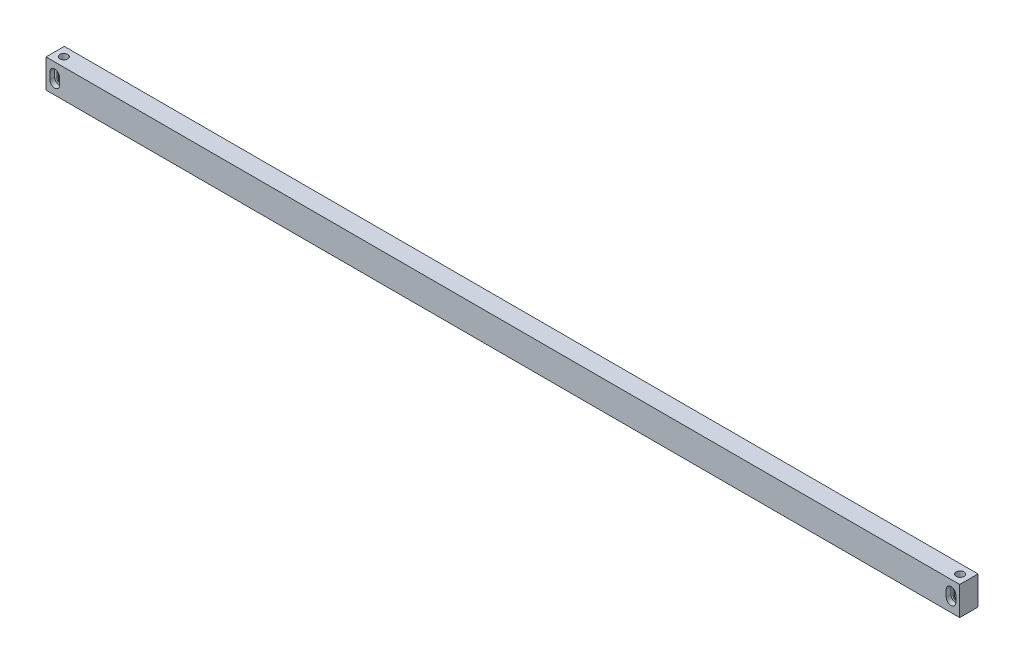
SolidWorks part; units mm, degrees
ref_plane "Front Plane" through (0, 0, 0) normal (0, 0, 1) x (1, 0, 0)
ref_plane "Top Plane" through (0, 0, 0) normal (0, 1, 0) x (1, 0, 0)
ref_plane "Right Plane" through (0, 0, 0) normal (1, 0, 0) x (0, 0, -1)
sketch "Sketch1" plane through (0, 0, 0) normal (0, 0, 1) x (1, 0, 0)
  line L0 (505, 33) -> (505, 0) construction
  line L1 (0, 0) -> (1010, 0)
  line L2 (0, 0) -> (0, 33)
  line L3 (0, 33) -> (1010, 33)
  line L4 (1010, 0) -> (1010, 33)
  line L5 (0, 0) -> (-20, 0)
  line L6 (0, 0) -> (0, 33)
  line L7 (0, 33) -> (-20, 33)
  line L8 (-20, 0) -> (-20, 33)
  line L9 (1010, 33) -> (1030, 33)
  line L10 (1010, 33) -> (1010, 0)
  line L11 (1010, 0) -> (1030, 0)
  line L12 (1030, 33) -> (1030, 0)
  line L13 (-10, 20.5) -> (-10, 12.5) construction
  line L14 (-7, 20.5) -> (-7, 12.5)
  line L15 (-13, 20.5) -> (-13, 12.5)
  line L16 (-4.5, 20.5) -> (-4.5, 12.5)
  line L17 (-15.5, 20.5) -> (-15.5, 12.5)
  line L18 (1020, 20.5) -> (1020, 12.5) construction
  line L19 (1017, 20.5) -> (1017, 12.5)
  line L20 (1023, 20.5) -> (1023, 12.5)
  line L21 (1025.5, 20.5) -> (1025.5, 12.5)
  line L22 (1014.5, 20.5) -> (1014.5, 12.5)
  arc A0 (-7, 20.5) -> (-13, 20.5) centre (-10, 20.5) ccw
  arc A1 (-13, 12.5) -> (-7, 12.5) centre (-10, 12.5) ccw
  arc A2 (-15.5, 12.5) -> (-4.5, 12.5) centre (-10, 12.5) ccw
  arc A3 (-4.5, 20.5) -> (-15.5, 20.5) centre (-10, 20.5) ccw
  arc A4 (1017, 20.5) -> (1023, 20.5) centre (1020, 20.5) cw
  arc A5 (1023, 12.5) -> (1017, 12.5) centre (1020, 12.5) cw
  arc A6 (1014.5, 20.5) -> (1025.5, 20.5) centre (1020, 20.5) cw
  arc A7 (1025.5, 12.5) -> (1014.5, 12.5) centre (1020, 12.5) cw
  point P13 (-10, 16.5)
  point P19 (0, 16.5)
  point P21 (-10, 33)
  point P30 (1020, 16.5)
  dimension "D4" = 3
  dimension "D1" = 1010
  dimension "D2" = 33
  dimension "D3" = 1050
  dimension "D5" = 8
  dimension "D6" = 2.5
extrude "Boss-Extrude1" add sketch "Sketch1" along normal mid plane 21 contours A7 L21 A6 L22 L20 A5 L19 A4 | L12 L9 L4 L11 L21 A7 L22 A6 | L1 L4 L3 L2 | L8 L5 L2 L7 A3 L16 A2 L17 | L16 A3 L17 A2 A1 L15 A0 L14 region at (505, 16.5, 0) region at (-10, 0.3859, 0) region at (1010.3859, 16.5, 0) region at (-4.7195, 16.5, 0) region at (1025.2805, 16.5, 0)
extrude "Cut-Extrude1" cut sketch "Sketch1<3>" along normal blind 21 from offset 5 contours L16 A3 L17 A2 A1 L15 A0 L14 | A7 L21 A6 L22 L20 A5 L19 A4 region at (-4.7195, 16.5, 0) region at (1025.2805, 16.5, 0)
sketch "Sketch1<3>" plane through (0, 0, 0) normal (0, 0, 1) x (1, 0, 0) same geometry as "Sketch1"
mirror "Mirror1" about plane through (0, 0, 0) normal (0, 0, 1) of "Cut-Extrude1"
hole_wizard "Ø9.0 (9) Diameter Hole1" positions "Sketch2" profile "Sketch3" hole size "Ø9.0" standard "ANSI Metric" end condition through all
sketch "Sketch2" plane through (0, 33, 0) normal (0, 1, 0) x (1, 0, 0)
  line L0 (-10, 10.5) -> (-10, -10.5) construction
  line L1 (-20, 10.5) -> (1030, 10.5) construction
  line L2 (-20, -10.5) -> (1030, -10.5) construction
  line L4 (-13, -5) -> (-7, -5) construction
  line L5 (-13, -5) -> (-7, -5) construction
  line L6 (505, 10.5) -> (505, -10.5) construction
  point P0 (-10, 0)
  point P14 (-10, -5)
  point P23 (1020, 0)
sketch "Sketch3" plane through (-10, 33, 0) normal (1, 0, 0) x (0, 0, 1)
  line L0 (0, 0) -> (0, 33)
  line L1 (0, 33) -> (4.5, 33)
  line L2 (4.5, 33) -> (4.5, 0)
  line L5 (4.5, 0) -> (0, 0)
  line L11 (0, -6.35) -> (0, 107.95) construction
  dimension "Thru Hole Dia." = 9
  dimension "Thru Hole Depth" = 33
